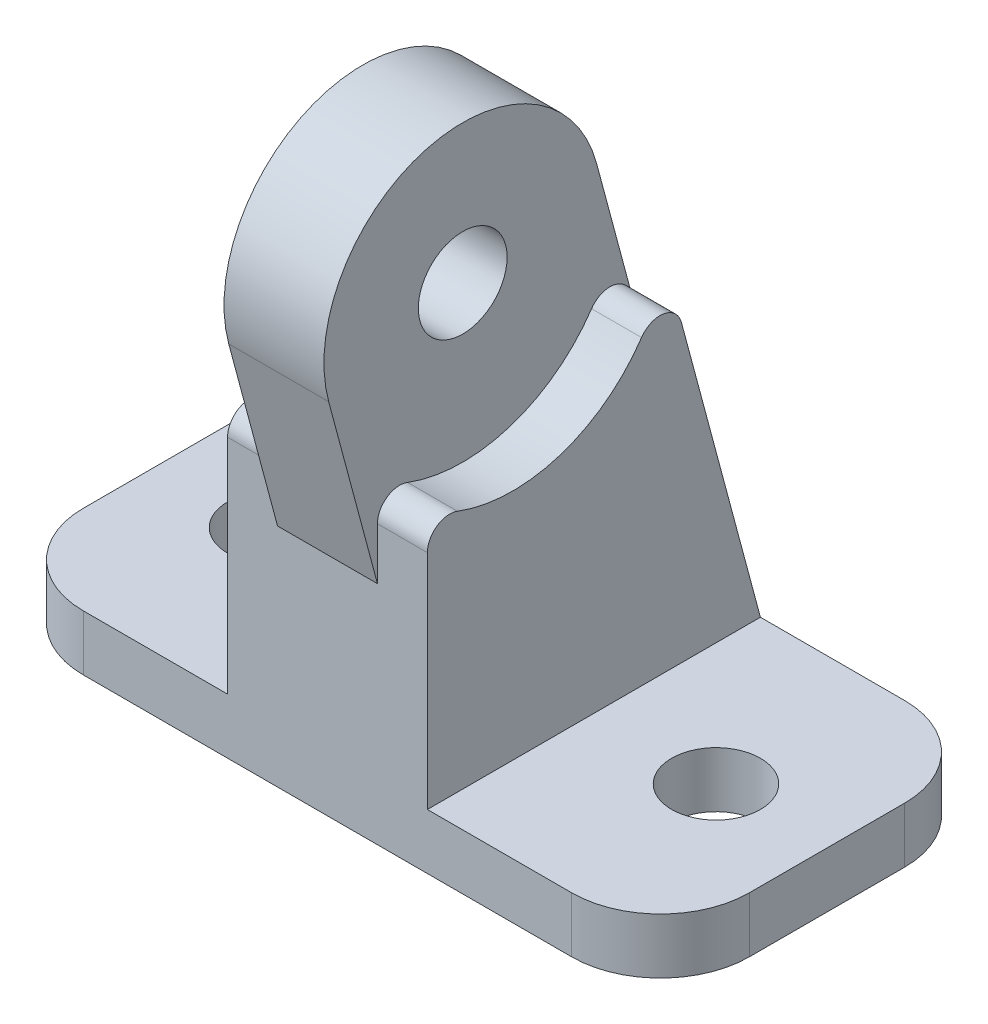
SolidWorks part; units mm, degrees
ref_plane "Front Plane" through (0, 0, 0) normal (0, 0, 1) x (1, 0, 0)
ref_plane "Top Plane" through (0, 0, 0) normal (0, 1, 0) x (1, 0, 0)
ref_plane "Right Plane" through (0, 0, 0) normal (1, 0, 0) x (0, 0, -1)
sketch "Sketch1" plane through (0, 0, 0) normal (0, 1, 0) x (1, 0, 0)
  line L0 (0, 0) -> (0, 18.8199) construction
  line L1 (-22, -15) -> (22, -15)
  line L2 (-30, -7) -> (-30, 7)
  line L3 (-22, 15) -> (22, 15)
  line L4 (30, -7) -> (30, 7)
  line L5 (-30, -15) -> (30, 15) construction
  line L6 (-30, 15) -> (30, -15) construction
  circle A0 centre (-20, 0) radius 4
  circle A1 centre (20, 0) radius 4
  arc A2 (-22, -15) -> (-30, -7) centre (-22, -7) cw
  arc A3 (22, -15) -> (30, -7) centre (22, -7) ccw
  arc A4 (22, 15) -> (30, 7) centre (22, 7) cw
  arc A5 (-30, 7) -> (-22, 15) centre (-22, 7) cw
  point P0 (0, 0)
  point P24 (0, 0)
  dimension "D3" = 20
  dimension "D4" = 8
  dimension "D5" = 8
  dimension "D1" = 30
  dimension "D2" = 60
extrude "Boss-Extrude1" add sketch "Sketch1" along normal blind 5
sketch "Sketch2" plane through (0, 0, 0) normal (1, 0, 0) x (0, 0, -1)
  line L0 (-15, 5) -> (-15, 28.2951)
  line L1 (15, 5) -> (15, 0) construction
  line L2 (6.3867, 37.1453) -> (15, 5)
  line L4 (6.3867, 37.1453) -> (4.7549, 43.2352)
  line L5 (-19.3932, 36.7648) -> (-15, 20.3689)
  line L6 (-15, 5) -> (15, 5)
  line L7 (-15, 0) -> (-7, 0) construction
  circle A0 centre (-7.3192, 40) radius 12.5
  circle A1 centre (-7.3192, 40) radius 4
  arc A3 (-15, 28.2951) -> (6.3867, 37.1453) centre (-7.3192, 40) ccw
  dimension "D1" = 25
  dimension "D2" = 40
  dimension "D4" = 8
  dimension "D5" = 28
  dimension "D3" = 15
extrude "Boss-Extrude2" add sketch "Sketch2" along normal mid plane 9 contours A3 L0 L6 L2 | L0 A3 L4 A0 L5 | A0 A1 region at (0, 16.4615, 0.9509) region at (0, 28.656, 16.8638) region at (0, 51.7326, 10.4629)
extrude "Boss-Extrude3" add sketch "Sketch2<4>" along normal mid plane 18 contours A3 L0 L6 L2 region at (0, 16.4615, 0.9509)
sketch "Sketch2<4>" plane through (0, 0, 0) normal (1, 0, 0) x (0, 0, -1) same geometry as "Sketch2"
fillet "Fillet1" radius 2 4 edges at (-6.75, 37.1453, -6.3867) (-6.75, 28.2951, 15) (6.75, 37.1453, -6.3867) (6.75, 28.2951, 15)
